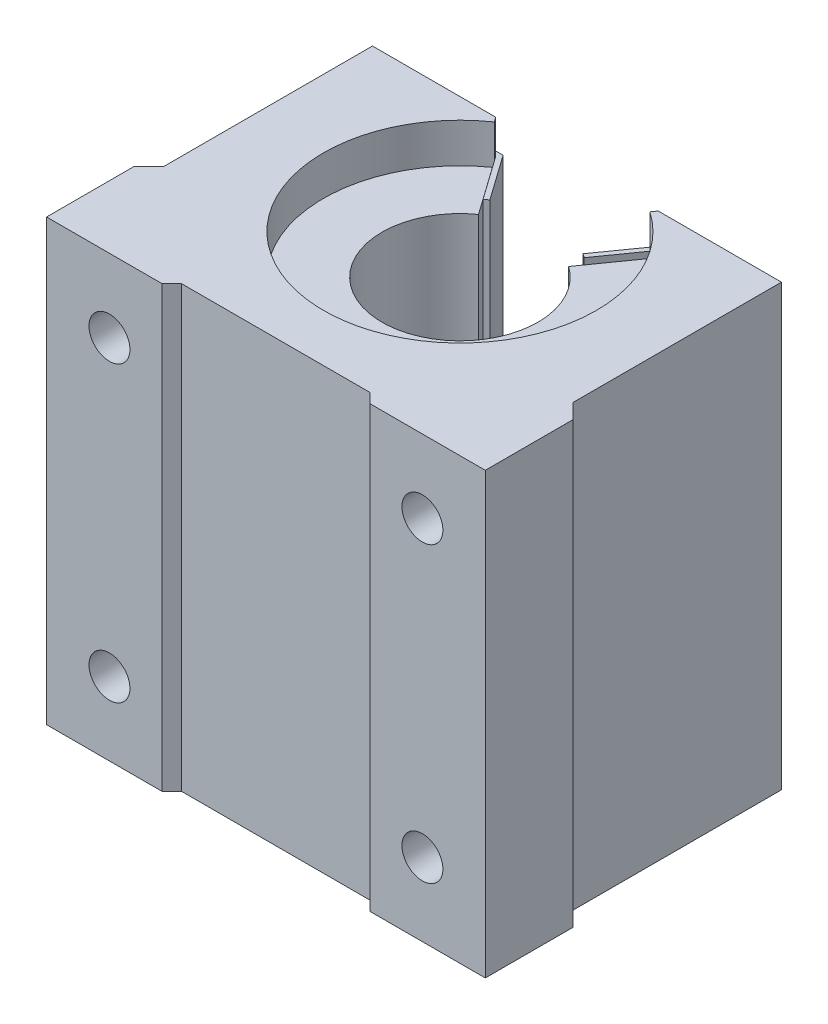
SolidWorks part; units mm, degrees
other "Camera1"
material "6061 Alloy"
ref_plane "Front Plane" through (0, 0, 0) normal (0, 0, 1) x (1, 0, 0)
ref_plane "Top Plane" through (0, 0, 0) normal (0, 1, 0) x (1, 0, 0)
ref_plane "Right Plane" through (0, 0, 0) normal (1, 0, 0) x (0, 0, -1)
sketch "Sketch1" plane through (0, 0, 0) normal (0, 1, 0) x (1, 0, 0)
  line L0 (0, -3.45) -> (0, -27.3078) construction
  line L1 (-20.975, 12) -> (20.975, 12)
  line L2 (-20.975, 12) -> (-20.975, -18.9)
  line L3 (-20.975, -18.9) -> (20.975, -18.9)
  line L4 (20.975, 12) -> (20.975, -18.9)
  line L5 (-20.975, 12) -> (20.975, -18.9) construction
  line L6 (-20.975, -18.9) -> (20.975, 12) construction
  line L7 (-20.975, -9.4) -> (-22.5, -10.925)
  line L8 (-22.5, -10.925) -> (-22.5, -19.9)
  line L9 (-22.5, -19.9) -> (-10.675, -19.9)
  line L10 (-10.675, -19.9) -> (-9.675, -18.9)
  line L11 (10.675, -19.9) -> (9.675, -18.9)
  line L12 (22.5, -19.9) -> (10.675, -19.9)
  line L13 (22.5, -10.925) -> (22.5, -19.9)
  line L14 (20.975, -9.4) -> (22.5, -10.925)
  line L15 (0, 0) -> (-8.5, 12)
  line L16 (0, 0) -> (8.5, 12)
  line L17 (-20.275, 12) -> (-20.275, 12.5)
  line L18 (-20.275, 12.5) -> (-8.075, 12.5)
  line L19 (-8.075, 12.5) -> (-4.7803, 7.8487)
  line L20 (-4.7803, 7.8487) -> (-5.1883, 7.5597)
  line L21 (-5.1883, 7.5597) -> (-8.3336, 12)
  line L22 (4.7803, 7.8487) -> (5.1883, 7.5597)
  line L23 (8.075, 12.5) -> (4.7803, 7.8487)
  line L24 (5.1883, 7.5597) -> (8.3336, 12)
  line L25 (20.275, 12.5) -> (8.075, 12.5)
  line L26 (20.275, 12) -> (20.275, 12.5)
  circle A0 centre (0, 0) radius 14
  circle A1 centre (0, 0) radius 8
  point P3 (0, -3.45)
  point P14 (0, -14)
  point P31 (-20.275, 12.25)
  dimension "D3" = 28
  dimension "D10" = 16
  dimension "D1" = 41.95
  dimension "D2" = 45
  dimension "D4" = 4.9
  dimension "D5" = 31.9
  dimension "D6" = 45
  dimension "D7" = 19.35
  dimension "D8" = 1
  dimension "D9" = 10.5
  dimension "D11" = 17
  dimension "D12" = 0.5
  dimension "D13" = 0.7
  dimension "D14" = 5.7
  dimension "D15" = 12.2
extrude "Main Body" add sketch "Sketch1" along normal mid plane 45.1 contours A0 L1 L2 L3 L4 | L14 L4 L3 L11 L12 L13 | L9 L10 L3 L2 L7 L8 | A0 L1 L15 | A0 L16 L1 region at (-20.625, 0, -11.479) region at (-21.1407, 0, 14.15) region at (-8.2284, 0, -11.7312) region at (15.325, 0, 19.0657) region at (8.2284, 0, -11.7312)
extrude "Rubber Bearing Sleeve" add sketch "Sketch1<3>" along normal mid plane 37 contours A1 L15 A0 L16 region at (-6.6668, 0, -8.7577)
sketch "Sketch1<3>" plane through (0, 0, 0) normal (0, 1, 0) x (1, 0, 0) same geometry as "Sketch1"
extrude "Boss-Extrude3" add sketch "Sketch1<4>" along normal mid plane 38.1 contours L1 L26 L25 L23 | L24 A0 L23 L22 | A0 L24 L1 L23 | L19 L18 L17 L1 | A0 L19 L1 L21 | L19 A0 L21 L20 region at (-14.086, 0, -12.2488) region at (-7.9338, 0, -11.8122) region at (-6.3792, 0, -9.6732) region at (14.086, 0, -12.2488) region at (7.9338, 0, -11.8122) region at (6.3792, 0, -9.6732)
sketch "Sketch1<4>" plane through (0, 0, 0) normal (0, 1, 0) x (1, 0, 0) same geometry as "Sketch1"
sketch "Sketch2" plane through (0, 0, 19.9) normal (0, 0, 1) x (1, 0, 0)
  line L1 (-16.05, 15.05) -> (16.05, 15.05) construction
  line L2 (-16.05, 15.05) -> (-16.05, -15.05) construction
  line L3 (-16.05, -15.05) -> (16.05, -15.05) construction
  line L4 (16.05, 15.05) -> (16.05, -15.05) construction
  line L5 (-16.05, 15.05) -> (16.05, -15.05) construction
  line L6 (-16.05, -15.05) -> (16.05, 15.05) construction
  point P0 (0, 0)
  dimension "D1" = 30.1
  dimension "D2" = 32.1
hole_wizard "M5x0.8 Tapped Hole1" positions "Sketch3" profile "Sketch4" tap size "M5x0.8" standard "ANSI Metric"
sketch "Sketch3" plane through (0, 0, 19.9) normal (0, 0, 1) x (1, 0, 0)
  point P0 (-16.05, 15.05)
  point P3 (16.05, 15.05)
  point P6 (16.05, -15.05)
  point P9 (-16.05, -15.05)
sketch "Sketch4" plane through (-16.05, 15.05, 19.9) normal (1, 0, 0) x (0, -1, 0)
  line L0 (0, 0) -> (0, 17.2618)
  line L1 (0, 17.2618) -> (2.1, 16)
  line L2 (2.1, 16) -> (2.1, 0)
  line L5 (2.1, 0) -> (0, 0)
  line L10 (0, 17.2618) -> (-2.1, 16) construction
  line L11 (0, -6.35) -> (0, 107.95) construction
  dimension "Tap Drill Dia." = 4.2
  dimension "Tap Drill Depth" = 16
  dimension "Drill Angle" = 118
cosmetic thread "Hole Thread1" parameters "D1"=10, "D2"=5
cosmetic thread "Hole Thread2" parameters "D1"=10, "D2"=5
cosmetic thread "Hole Thread3" parameters "D1"=10, "D2"=5
cosmetic thread "Hole Thread4" parameters "D1"=10, "D2"=5
